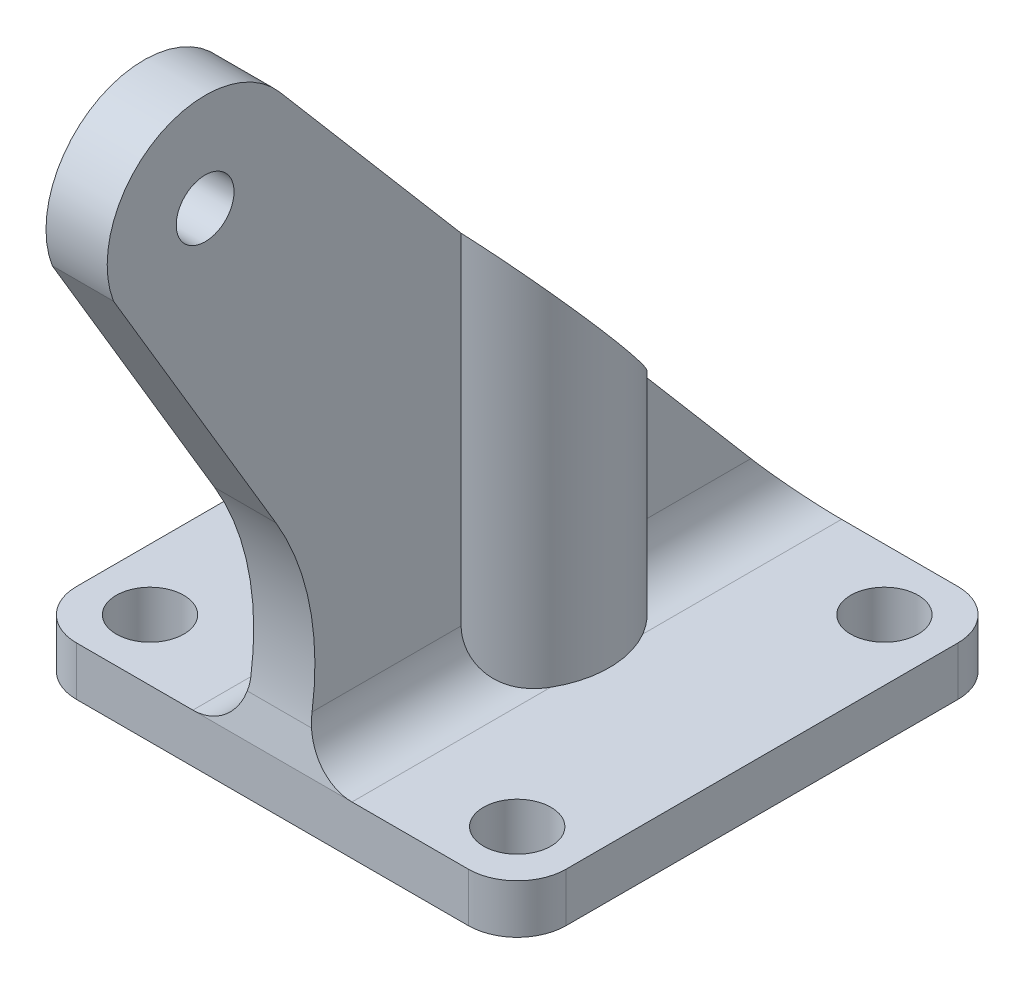
SolidWorks part; units mm, degrees
ref_plane "Front Plane" through (0, 0, 0) normal (0, 0, 1) x (1, 0, 0)
ref_plane "Top Plane" through (0, 0, 0) normal (0, 1, 0) x (1, 0, 0)
ref_plane "Right Plane" through (0, 0, 0) normal (1, 0, 0) x (0, 0, -1)
sketch "Sketch1" plane through (0, 0, 0) normal (0, 1, 0) x (1, 0, 0)
  line L1 (-12.7, 12.7) -> (12.7, 12.7)
  line L2 (-12.7, 12.7) -> (-12.7, -12.7)
  line L3 (-12.7, -12.7) -> (12.7, -12.7)
  line L4 (12.7, 12.7) -> (12.7, -12.7)
  line L5 (-12.7, 12.7) -> (12.7, -12.7) construction
  line L6 (-12.7, -12.7) -> (12.7, 12.7) construction
  point P0 (0, 0)
  dimension "D1" = 25.4
  dimension "D2" = 25.4
extrude "Boss-Extrude1" add sketch "Sketch1" along normal blind 2.54
sketch "Sketch3" plane through (0, 0, 0) normal (1, 0, 0) x (0, 0, -1)
  line L0 (-22.5349, 28.6918) -> (-14.1091, 14.5181)
  line L1 (-13.9132, 33.7746) -> (12.7, 2.54)
  line L2 (12.7, 2.54) -> (-12.7, 2.54)
  line L3 (-12.7, 0) -> (12.7, 0) construction
  line L4 (12.7, 2.54) -> (12.7, 0) construction
  line L5 (-12.3369, 4.4499) -> (-12.7, 2.54)
  arc A0 (-22.5349, 28.6918) -> (-13.9132, 33.7746) centre (-17.78, 30.48) cw
  circle A1 centre (-17.78, 30.48) radius 1.5
  arc A2 (-14.1091, 14.5181) -> (-12.3369, 4.4499) centre (-26.5122, 7.1449) cw
  dimension "D2" = 5.08
  dimension "D3" = 3
  dimension "D1" = 30.48
  dimension "D4" = 30.48
extrude "Boss-Extrude2" add sketch "Sketch3" along normal mid plane 3.175
fillet "Fillet1" radius 2.54 2 edges
fillet "Fillet2" radius 2.54 4 edges at (12.7, 1.27, -12.7) (12.7, 1.27, 12.7) (-12.7, 1.27, 12.7) (-12.7, 1.27, -12.7)
sketch "Sketch4" plane through (0, 0, 0) normal (0, -1, 0) x (1, 0, 0)
  circle A0 centre (0, 0) radius 3.5
  dimension "D1" = 7
extrude "Boss-Extrude3" add sketch "Sketch4" against normal blind 7
sketch "Sketch5" plane through (0, 0, 0) normal (0, -1, 0) x (1, 0, 0)
  circle A0 centre (0, 0) radius 1.75
  dimension "D1" = 3.5
extrude "Cut-Extrude1" cut sketch "Sketch5" against normal through all
sketch "Sketch6" plane through (0, 7, 0) normal (0, 1, 0) x (1, 0, 0)
  circle A0 centre (0, 0) radius 3.5
extrude "Cut-Extrude2" cut sketch "Sketch6" along normal through all and the other way blind 2
sketch "Sketch10" plane through (0, 2.54, 0) normal (0, 1, 0) x (1, 0, 0)
  circle A0 centre (0, 0) radius 3.5
  circle A1 centre (0, 0) radius 4.77
  dimension "D1" = 1.27
extrude "Boss-Extrude4" add sketch "Sketch10" along normal blind 21.844
sketch "Sketch8" plane through (1.5875, 0, 0) normal (1, 0, 0) x (0, 0, -1)
  line L0 (-9.9554, 29.1295) -> (6.7092, 9.5711)
  line L1 (-4.4981, 22.7245) -> (-13.9132, 33.7746) construction
  line L2 (10.5358, 5.08) -> (4.4981, 12.1662) construction
  line L3 (6.7092, 9.5711) -> (6.7092, 29.1295)
  line L4 (6.7092, 29.1295) -> (-9.9554, 29.1295)
sketch "Sketch9" plane through (0, 2.54, 0) normal (0, 1, 0) x (1, 0, 0)
  line L1 (9.525, -9.525) -> (-9.525, -9.525) construction
  line L2 (9.525, -9.525) -> (9.525, 9.525) construction
  line L3 (9.525, 9.525) -> (-9.525, 9.525) construction
  line L4 (-9.525, -9.525) -> (-9.525, 9.525) construction
  line L5 (9.525, -9.525) -> (-9.525, 9.525) construction
  line L6 (9.525, 9.525) -> (-9.525, -9.525) construction
  circle A0 centre (-9.525, -9.525) radius 1.75
  circle A1 centre (-9.525, 9.525) radius 1.75
  circle A2 centre (9.525, 9.525) radius 1.75
  circle A3 centre (9.525, -9.525) radius 1.75
  point P0 (0, 0)
  dimension "D3" = 3.5
  dimension "D1" = 19.05
  dimension "D2" = 19.05
extrude "Cut-Extrude4" cut sketch "Sketch9" against normal through all
extrude "Cut-Extrude5" cut sketch "Sketch8" against normal through all and the other way through all
